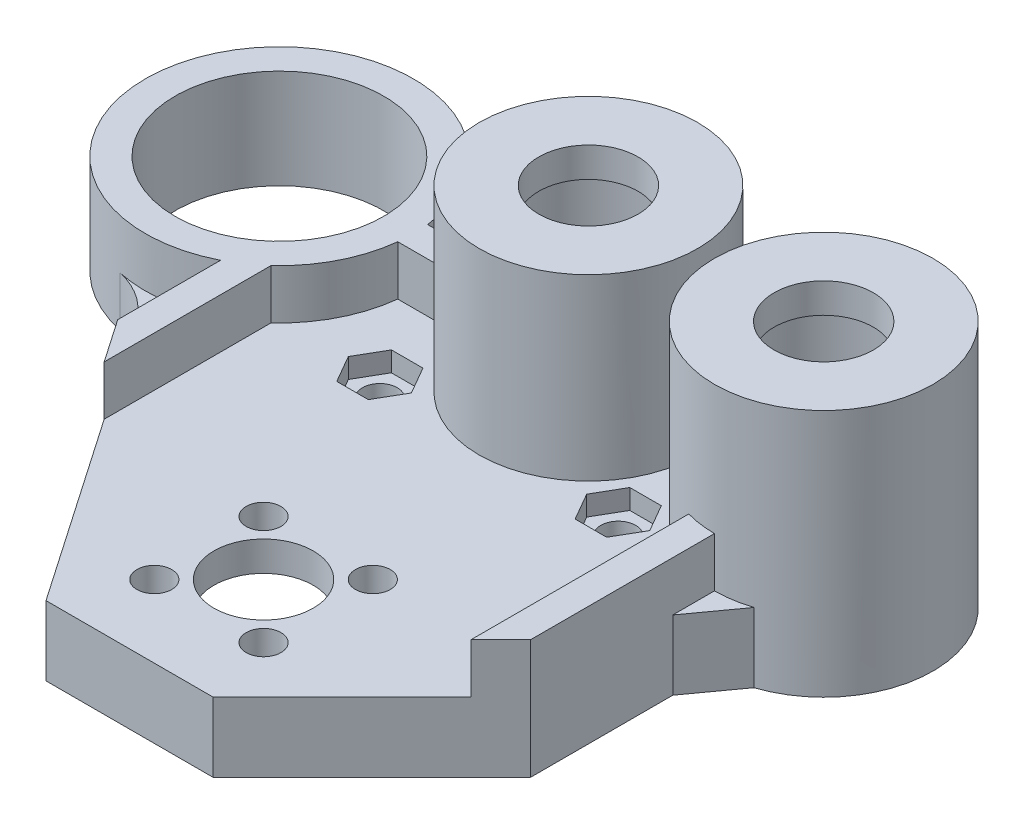
SolidWorks part; units mm, degrees
ref_plane "Front Plane" through (0, 0, 0) normal (0, 0, 1) x (1, 0, 0)
ref_plane "Top Plane" through (0, 0, 0) normal (0, 1, 0) x (1, 0, 0)
ref_plane "Right Plane" through (0, 0, 0) normal (1, 0, 0) x (0, 0, -1)
sketch "Sketch3" plane through (0, 0, 0) normal (0, 1, 0) x (1, 0, 0)
  line L1 (-31.113, 13.5) -> (23.69, 13.5)
  line L2 (-31.113, 13.5) -> (-31.113, -13.5)
  line L3 (-31.113, -13.5) -> (23.69, -13.5)
  line L4 (23.69, 13.5) -> (23.69, -13.5)
  line L5 (23.69, -13.5) -> (-31.113, -13.5)
  line L6 (23.69, -13.5) -> (23.69, -45.5)
  line L7 (23.69, -45.5) -> (-31.113, -45.5)
  line L8 (-31.113, -13.5) -> (-31.113, -45.5)
  circle A0 centre (-31.113, 0) radius 10.5
  circle A1 centre (-31.113, 0) radius 13.5
  circle A2 centre (0, -32.7076) radius 5
  circle A3 centre (0, 0) radius 8
  circle A4 centre (23.69, 0) radius 8
  circle A5 centre (23.69, 0) radius 11
  dimension "D1" = 27
  dimension "D2" = 21
  dimension "D5" = 10
  dimension "D6" = 16
  dimension "D7" = 16
  dimension "D9" = 22
  dimension "D3" = 31.113
  dimension "D4" = 23.69
  dimension "D8" = 23.69
  dimension "D10" = 32
  dimension "D11" = 27
extrude "Boss-Extrude1" add sketch "Sketch3" along normal blind 7 contours L2 A1 A0 | A5 L4 L1 A1 L3 A3 | L2 A1 A0 | L4 A5 A4 | L3 L8 L7 L6 A2 | L4 A5 A4 region at (-21.7805, 0, -9.3325) region at (-3.7115, 0, -12.8891) region at (-31.4149, 0, -12) region at (-3.8855, 0, 29.3496) region at (31.2942, 0, -7.6042) region at (23.444, 0, -9.5)
sketch "Sketch4" plane through (0, 0, 0) normal (0, 1, 0) x (1, 0, 0)
  circle A0 centre (5.5, -27.2076) radius 1.75
  circle A1 centre (0, -32.7076) radius 5 construction
  circle A2 centre (5.5, -38.2076) radius 1.75
  circle A3 centre (-5.5, -38.2076) radius 1.75
  circle A4 centre (-5.5, -27.2076) radius 1.75
  dimension "D3" = 3.5
  dimension "D4" = 3.5
  dimension "D7" = 3.5
  dimension "D9" = 3.5
  dimension "D1" = 5.5
  dimension "D2" = 5.5
  dimension "D5" = 5.5
  dimension "D6" = 5.5
  dimension "D8" = 11
extrude "Cut-Extrude3" cut sketch "Sketch4" along normal through all both and the other way through all
sketch "Sketch6" plane through (0, 7, 0) normal (0, 1, 0) x (1, 0, 0)
  circle A0 centre (23.69, 0) radius 8 construction
  circle A1 centre (0, 0) radius 8 construction
  circle A2 centre (23.69, 0) radius 8
  circle A3 centre (0, 0) radius 8
  circle A4 centre (23.69, 0) radius 11
  circle A5 centre (0, 0) radius 11
  dimension "D1" = 22
extrude "Boss-Extrude2" add sketch "Sketch6" along normal blind 15
sketch "Sketch7" plane through (0, 22, 0) normal (0, 1, 0) x (1, 0, 0)
  circle A0 centre (23.69, 0) radius 11 construction
  circle A1 centre (0, 0) radius 11 construction
  circle A2 centre (23.69, 0) radius 11
  circle A3 centre (0, 0) radius 11
  circle A4 centre (0, 0) radius 5
  circle A5 centre (23.69, 0) radius 5
  dimension "D1" = 10
  dimension "D2" = 10
extrude "Boss-Extrude3" add sketch "Sketch7" along normal blind 3
chamfer "Chamfer1" distance 2.5 angle 45 1 edges at (23.69, 3.5, -11)
sketch "Sketch8" plane through (0, 0, 0) normal (0, 1, 0) x (1, 0, 0)
  line L0 (-31.113, 0) -> (-31.113, 12.25)
  line L1 (-31.113, -13.5) -> (-51.113, -13.5)
  line L2 (-31.113, -13.5) -> (-31.113, 13.5)
  line L3 (-31.113, 13.5) -> (-51.113, 13.5)
  line L4 (-51.113, -13.5) -> (-51.113, 13.5)
  line L5 (-31.113, 12.25) -> (-13.613, 6.5)
  line L6 (-13.613, 6.5) -> (-13.613, -6.5)
  line L7 (-13.613, -6.5) -> (-31.113, -12.25)
  line L8 (-31.113, -12.25) -> (-31.113, 0)
  dimension "D1" = 20
  dimension "D2" = 12.25
  dimension "D3" = 12.25
  dimension "D4" = 27
  dimension "D5" = 17.5
  dimension "D6" = 6.5
  dimension "D7" = 6.5
extrude "Cut-Extrude4" cut sketch "Sketch8" along normal blind 2 contours L4 L1 L2 L0 L3 | L7 L6 L5 L0 L2 region at (-41.113, 0, 0) region at (-23.2574, 0, 0)
sketch "Sketch9" plane through (0, 0, 0) normal (0, 1, 0) x (1, 0, 0)
  circle A0 centre (12, 9) radius 1.75
  circle A1 centre (12, -9) radius 1.75
  circle A2 centre (-12, -9) radius 1.75
  circle A3 centre (-12, 9) radius 1.75
  dimension "D3" = 3.5
  dimension "D4" = 3.5
  dimension "D6" = 3.5
  dimension "D8" = 12
  dimension "D9" = 3.5
  dimension "D1" = 12
  dimension "D2" = 9
  dimension "D5" = 9
  dimension "D7" = 12
extrude "Cut-Extrude5" cut sketch "Sketch9" along normal through all both and the other way through all
sketch "Sketch10" plane through (0, 7, 0) normal (0, 1, 0) x (1, 0, 0)
  line L1 (-15.1754, -9) -> (-13.5877, -11.75)
  line L2 (-13.5877, -11.75) -> (-10.4123, -11.75)
  line L3 (-10.4123, -11.75) -> (-8.8246, -9)
  line L4 (-8.8246, -9) -> (-10.4123, -6.25)
  line L5 (-10.4123, -6.25) -> (-13.5877, -6.25)
  line L6 (-13.5877, -6.25) -> (-15.1754, -9)
  line L7 (-15.1754, 9) -> (-13.5877, 6.25)
  line L8 (-13.5877, 6.25) -> (-10.4123, 6.25)
  line L9 (-10.4123, 6.25) -> (-8.8246, 9)
  line L10 (-8.8246, 9) -> (-10.4123, 11.75)
  line L11 (-10.4123, 11.75) -> (-13.5877, 11.75)
  line L12 (-13.5877, 11.75) -> (-15.1754, 9)
  line L13 (15.1754, 9) -> (13.5877, 11.75)
  line L14 (13.5877, 11.75) -> (10.4123, 11.75)
  line L15 (10.4123, 11.75) -> (8.8246, 9)
  line L16 (8.8246, 9) -> (10.4123, 6.25)
  line L17 (10.4123, 6.25) -> (13.5877, 6.25)
  line L18 (13.5877, 6.25) -> (15.1754, 9)
  line L19 (15.1754, -9) -> (13.5877, -6.25)
  line L20 (13.5877, -6.25) -> (10.4123, -6.25)
  line L21 (10.4123, -6.25) -> (8.8246, -9)
  line L22 (8.8246, -9) -> (10.4123, -11.75)
  line L23 (10.4123, -11.75) -> (13.5877, -11.75)
  line L24 (13.5877, -11.75) -> (15.1754, -9)
  circle A0 centre (12, -9) radius 1.75 construction
  circle A1 centre (12, 9) radius 1.75 construction
  circle A2 centre (-12, 9) radius 1.75 construction
  circle A3 centre (-12, -9) radius 1.75 construction
  circle A4 centre (12, -9) radius 1.75
  circle A5 centre (12, 9) radius 1.75
  circle A6 centre (-12, 9) radius 1.75
  circle A7 centre (-12, -9) radius 1.75
  circle A8 centre (-12, -9) radius 2.75 construction
  circle A9 centre (-12, 9) radius 2.75 construction
  circle A10 centre (12, 9) radius 2.75 construction
  circle A11 centre (12, -9) radius 2.75 construction
  dimension "D1" = 5.5
  dimension "D2" = 5.5
  dimension "D3" = 5.5
  dimension "D4" = 5.5
extrude "Cut-Extrude6" cut sketch "Sketch10" against normal blind 2
chamfer "Chamfer2" distance 5 angle 45 1 edges at (23.69, 3.5, 11)
chamfer "Chamfer3" distance 32 distance2 22 1 edges at (-31.113, 3.5, 45.5) first distance on face at (-31.113, 3, 23.75)
chamfer "Chamfer4" distance 16 angle 45 1 edges at (23.69, 3.5, 45.5)
fillet "Fillet1" radius 8 1 edges at (-31.113, 4.5, 13.5)
sketch "Sketch12" plane through (0, 7, 0) normal (0, 1, 0) x (1, 0, 0)
  line L1 (-19.4184, -1.5) -> (-9.2882, -1.5)
  line L2 (-19.4184, -1.5) -> (-19.4184, 1.5)
  line L3 (-19.4184, 1.5) -> (-9.2882, 1.5)
  line L4 (-9.2882, -1.5) -> (-9.2882, 1.5)
  line L5 (13.6189, -1.5) -> (8.9767, -1.5)
  line L6 (13.6189, -1.5) -> (13.6189, 1.5)
  line L7 (13.6189, 1.5) -> (8.9767, 1.5)
  line L8 (8.9767, -1.5) -> (8.9767, 1.5)
  arc A0 (26.5751, 10.6149) -> (27.1275, -10.4491) centre (23.69, 0) ccw construction
  circle A1 centre (0, 0) radius 11 construction
  circle A2 centre (-31.113, 0) radius 10.5 construction
  arc A3 (26.5751, 10.6149) -> (27.1275, -10.4491) centre (23.69, 0) ccw
  circle A4 centre (0, 0) radius 11
  circle A5 centre (-31.113, 0) radius 10.5
  circle A6 centre (-31.113, 0) radius 13.5
  circle M30 centre (-31.113, 0) radius 10.5
  arc M39 (27.1275, -10.4491) -> (26.5751, 10.6149) centre (23.69, 0) cw
  arc M42 (-31.113, 13.5) -> (-33.9648, -13.1953) centre (-31.113, 0) ccw
  circle M45 centre (0, 0) radius 11
  dimension "D1" = 3
  dimension "D2" = 1.5
extrude "Boss-Extrude4" add sketch "Sketch12" along normal blind 5 contours L7 L5 M39 M45 | A6 L1 L3 M45 | L3 A6 L1 L2 M42 M30 | L1 A6 L3 L2 region at (-18.5295, 7, 0) region at (-18.5575, 7, 1.8812) region at (-14.3033, 7, 0) region at (11.845, 7, 0)
sketch "Sketch13" plane through (0, 7, 0) normal (0, 1, 0) x (1, 0, 0)
  line L0 (23.69, -15.1987) -> (23.69, -29.5) construction
  line L1 (23.69, -15.1987) -> (23.69, -29.5)
  line L3 (23.69, -37.58) -> (20.69, -37.58)
  line L4 (23.69, -37.58) -> (23.69, 1.8154)
  line L5 (23.69, 1.8154) -> (20.69, 1.8154)
  line L6 (20.69, -37.58) -> (20.69, 1.8154)
  line L7 (-22, -2.4764) -> (-25, -2.4764)
  line L8 (-22, -2.4764) -> (-22, -39.8517)
  line L9 (-22, -39.8517) -> (-25, -39.8517)
  line L10 (-25, -2.4764) -> (-25, -39.8517)
  line L17 (-10.8972, -1.5) -> (-17.6966, -1.5)
  line L18 (-29.0625, -16.4826) -> (-9.113, -45.5)
  line L19 (-9.113, -45.5) -> (7.69, -45.5)
  line L20 (7.69, -45.5) -> (23.69, -29.5)
  line L21 (23.69, -29.5) -> (23.69, -15.1987)
  line L22 (23.69, -15.1987) -> (27.1275, -10.4491)
  line L23 (12.7928, -1.5) -> (10.8972, -1.5)
  line L24 (-10.8972, -1.5) -> (-17.6966, -1.5)
  line L25 (-29.0625, -16.4826) -> (-9.113, -45.5)
  line L26 (-9.113, -45.5) -> (7.69, -45.5)
  line L27 (7.69, -45.5) -> (23.69, -29.5)
  line L28 (23.69, -29.5) -> (23.69, -15.1987)
  line L29 (23.69, -15.1987) -> (27.1275, -10.4491)
  line L30 (12.7928, -1.5) -> (10.8972, -1.5)
  arc A3 (-33.9648, -13.1953) -> (-17.6966, -1.5) centre (-31.113, 0) ccw
  arc A4 (-33.9648, -13.1953) -> (-17.6966, -1.5) centre (-31.113, 0) ccw
  arc A6 (12.7928, -1.5) -> (27.1275, -10.4491) centre (23.69, 0) ccw
  arc A7 (-10.8972, -1.5) -> (10.8972, -1.5) centre (0, 0) ccw
  arc A8 (-29.0625, -16.4826) -> (-33.9648, -13.1953) centre (-35.6548, -21.0148) ccw
  arc A9 (-29.0625, -16.4826) -> (-33.9648, -13.1953) centre (-35.6548, -21.0148) ccw
  arc A10 (12.7928, -1.5) -> (27.1275, -10.4491) centre (23.69, 0) ccw
  arc A11 (-10.8972, -1.5) -> (10.8972, -1.5) centre (0, 0) ccw
  arc M39 (-17.6966, -1.5) -> (-33.9648, -13.1953) centre (-31.113, 0) cw
  line M41 (-29.0625, -16.4826) -> (-9.113, -45.5)
  line M43 (7.69, -45.5) -> (23.69, -29.5)
  line M44 (23.69, -29.5) -> (23.69, -15.1987)
  arc M46 (27.1275, -10.4491) -> (12.7928, -1.5) centre (23.69, 0) cw
  dimension "D2" = 3
  dimension "D3" = 3
  dimension "D4" = 22
  dimension "D5" = 0
  dimension "D1" = 0
extrude "Boss-Extrude5" add sketch "Sketch13" along normal blind 5 contours L6 L4 M43 M44 M46 | L10 L8 M39 M41 region at (22.1476, 7, 20.9493) region at (-23.3807, 7, 17.8818)
sketch "Sketch14" plane through (0, 0, 0) normal (0, -1, 0) x (1, 0, 0)
  line L12 (23.69, 15.1987) -> (23.69, 29.5)
  line L13 (23.69, 29.5) -> (7.69, 45.5)
  line L14 (7.69, 45.5) -> (-9.113, 45.5)
  line L15 (-9.113, 45.5) -> (-31.113, 13.5)
  line L16 (-31.113, 13.5) -> (-31.113, 12.25)
  line L17 (-31.113, 12.25) -> (-13.613, 6.5)
  line L18 (-13.613, 6.5) -> (-13.613, -6.5)
  line L19 (-13.613, -6.5) -> (-31.113, -12.25)
  line L20 (-31.113, -12.25) -> (-31.113, -13.5)
  line L21 (-31.113, -13.5) -> (23.69, -13.5)
  line L22 (23.69, -13.5) -> (26.5751, -10.6149)
  line L23 (27.1275, 10.4491) -> (23.69, 15.1987)
  line L24 (23.69, 15.1987) -> (23.69, 29.5)
  line L25 (23.69, 29.5) -> (7.69, 45.5)
  line L26 (7.69, 45.5) -> (-9.113, 45.5)
  line L27 (-9.113, 45.5) -> (-31.113, 13.5)
  line L28 (-31.113, 13.5) -> (-31.113, 12.25)
  line L29 (-31.113, 12.25) -> (-13.613, 6.5)
  line L30 (-13.613, 6.5) -> (-13.613, -6.5)
  line L31 (-13.613, -6.5) -> (-31.113, -12.25)
  line L32 (-31.113, -12.25) -> (-31.113, -13.5)
  line L33 (-31.113, -13.5) -> (23.69, -13.5)
  line L34 (23.69, -13.5) -> (26.5751, -10.6149)
  line L35 (27.1275, 10.4491) -> (23.69, 15.1987)
  circle A0 centre (0, 32.7076) radius 5 construction
  arc A1 (26.5751, -10.6149) -> (27.1275, 10.4491) centre (23.69, 0) ccw
  arc A2 (26.5751, -10.6149) -> (27.1275, 10.4491) centre (23.69, 0) ccw
  circle A3 centre (0, 32.7076) radius 5
  circle A4 centre (0, 32.7076) radius 11.5
  circle M19 centre (0, 32.7076) radius 5
  circle M22 centre (5.5, 27.2076) radius 1.75
  circle M23 centre (5.5, 38.2076) radius 1.75
  circle M24 centre (-5.5, 38.2076) radius 1.75
  circle M25 centre (-5.5, 27.2076) radius 1.75
  dimension "D2" = 23
  dimension "D1" = 0
extrude "Cut-Extrude8" cut sketch "Sketch14" against normal blind 4 contours A4 M19 M23 M25 M24 M22 region at (-11.1747, 0, 32.7076)
fillet "Fillet2" radius 3 2 edges at (-31.113, 1, -12.25) (-31.113, 1, 12.25)
